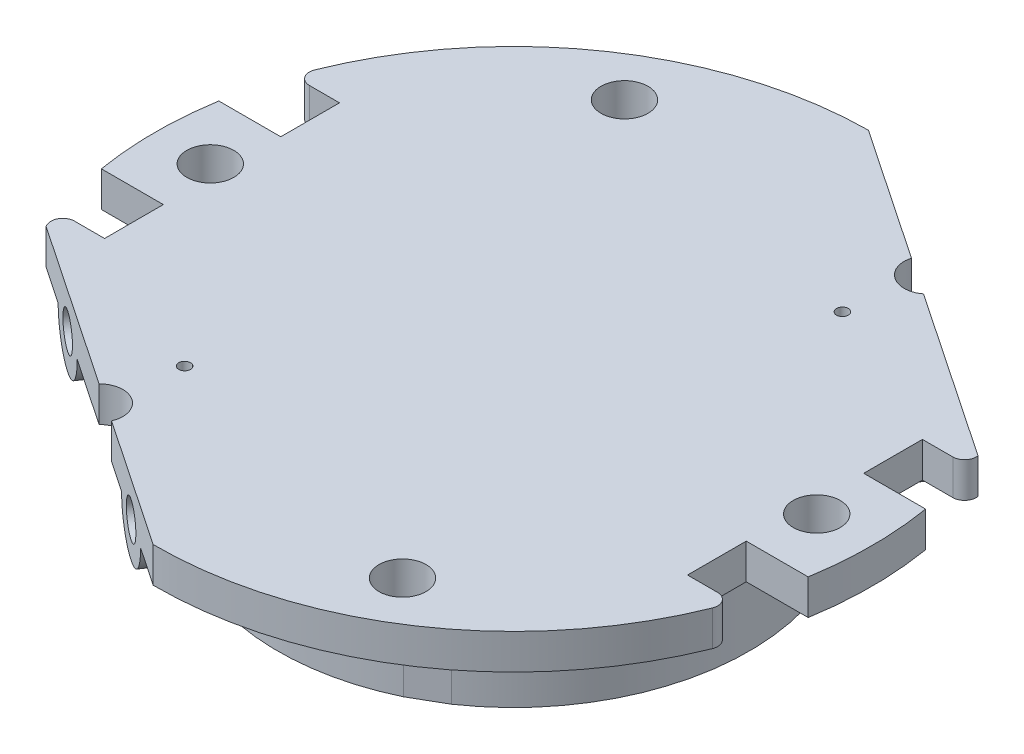
SolidWorks part; units mm, degrees
ref_plane "Alzado" through (0, 0, 0) normal (0, 0, 1) x (1, 0, 0)
ref_plane "Planta" through (0, 0, 0) normal (0, 1, 0) x (1, 0, 0)
ref_plane "Vista lateral" through (0, 0, 0) normal (1, 0, 0) x (0, 0, -1)
sketch "Croquis1" plane through (0, 0, 0) normal (0, 1, 0) x (1, 0, 0)
  circle A0 centre (0, 0) radius 30.5
extrude "Saliente-Extruir1" add sketch "Croquis1" along normal blind 3
sketch "Croquis5" plane through (0, 3, 0) normal (0, 1, 0) x (1, 0, 0)
  line L1 (28.8141, -5) -> (30.0874, -5)
  line L2 (28.8141, 5) -> (30.0874, 5)
  line L3 (-24.8141, 10) -> (-28.8141, 10)
  line L4 (24.8141, -5) -> (24.8141, -10)
  line L5 (-24.8141, -10) -> (-28.8141, -10)
  line L6 (24.8141, -5) -> (28.8141, -5)
  line L7 (24.8141, 5) -> (24.8141, 10)
  line L8 (-24.8141, 5) -> (-28.8141, 5)
  line L9 (-24.8141, 5) -> (-24.8141, 10)
  line L10 (-24.8141, -5) -> (-28.8141, -5)
  line L11 (-24.8141, -5) -> (-24.8141, -10)
  line L12 (24.8141, 5) -> (28.8141, 5)
  line L13 (24.8141, -10) -> (28.8141, -10)
  line L14 (24.8141, 10) -> (28.8141, 10)
  line L15 (-28.8141, 5) -> (-30.0874, 5)
  line L16 (-28.8141, -5) -> (-30.0874, -5)
  line L18 (-24.8141, 0) -> (-12.407, -21.4896)
  line L19 (-12.407, -21.4896) -> (12.407, -21.4896)
  line L20 (12.407, -21.4896) -> (24.8141, 0)
  line L21 (24.8141, 0) -> (12.407, 21.4896)
  line L22 (12.407, 21.4896) -> (-12.407, 21.4896)
  line L23 (-12.407, 21.4896) -> (-24.8141, 0)
  circle A0 centre (0, 0) radius 21.4896 construction
  circle A1 centre (0, 0) radius 30.5 construction
  arc A2 (-28.8141, 10) -> (-30.0874, 5) centre (0, 0) ccw
  arc A4 (-30.0874, -5) -> (-28.8141, -10) centre (0, 0) ccw
  arc A5 (30.0874, -5) -> (28.8141, -10) centre (0, 0) cw
  arc A6 (28.8141, 10) -> (30.0874, 5) centre (0, 0) cw
  circle M2 centre (0, 0) radius 30.5
extrude "Cortar-Extruir3" cut sketch "Croquis5" against normal blind 4 contours L10 L16 L5 L11 M2 | L15 L8 L9 L3 M2 | L14 L7 L12 L2 M2 | L4 L13 L1 L6 M2 region at (27.1844, 3, 7.3876) region at (-27.1844, 3, 7.3876) region at (27.1844, 3, -7.3876) region at (-27.1844, 3, -7.3876)
sketch "Croquis7" plane through (0, 3, 0) normal (0, 1, 0) x (1, 0, 0)
  line L2 (25.8141, 0) -> (12.907, 22.3556)
  line L3 (12.907, 22.3556) -> (-12.907, 22.3556)
  line L4 (-12.907, 22.3556) -> (-25.8141, 0)
  line L5 (-25.8141, 0) -> (-12.907, -22.3556)
  line L6 (-12.907, -22.3556) -> (12.907, -22.3556)
  line L7 (12.907, -22.3556) -> (25.8141, 0)
  circle A0 centre (25.8141, 0) radius 2
  circle A4 centre (-25.8141, 0) radius 2
  circle A5 centre (0, 0) radius 22.3556 construction
  circle A6 centre (12.907, 22.3556) radius 2
  circle A7 centre (-12.907, -22.3556) radius 2
  circle A8 centre (-12.907, 22.3556) radius 2
  circle A9 centre (12.907, -22.3556) radius 2
extrude "Cortar-Extruir4" cut sketch "Croquis7" against normal blind 10 contours A8 L4 L3 | A4 L4 L5 | A4 L5 L4 | A8 L3 L4 | L2 A6 L3 | L3 A6 L2 | L7 A0 L2 | L2 A0 L7 | A7 L5 L6 | A7 L6 L5 | L6 A9 L7 | L7 A9 L6 | A4 region at (24.7114, 3, 0) region at (26.3654, 3, 0) region at (12.3557, 3, -21.4007) region at (13.1827, 3, -22.8331) region at (13.1827, 3, 22.8331) region at (12.3557, 3, 21.4007) region at (-12.3557, 3, -21.4007) region at (-13.1827, 3, -22.8331) region at (-13.1827, 3, 22.8331) region at (-12.3557, 3, 21.4007) region at (-24.7114, 3, 0) region at (-26.3654, 3, 0)
sketch "Croquis8" plane through (0, 3, 0) normal (0, 1, 0) x (1, 0, 0)
  line L0 (0, 0) -> (12, 0)
  line L1 (12, 0) -> (12, 16)
  line L2 (0, 0) -> (-12, 0)
  line L3 (-12, 0) -> (-12, -16)
  circle A0 centre (12, 16) radius 0.5
  circle A1 centre (-12, -16) radius 0.5
extrude "Cortar-Extruir5" cut sketch "Croquis8" against normal blind 3 contours A1 | A0 region at (11.6564, 3, -16.3436) region at (-11.6564, 3, 15.6564)
sketch "Croquis9" plane through (0, 3, 0) normal (0, 1, 0) x (1, 0, 0)
  line L2 (-10, 17.3205) -> (-8.701, 18.0705)
  line L5 (25.6318, 16.5306) -> (27.1318, 13.9325)
  line L6 (-10, 17.3205) -> (-11.299, 16.5705)
  line L8 (10, -17.3205) -> (8.701, -18.0705)
  line L9 (10, -17.3205) -> (11.299, -16.5705)
  circle A0 centre (0, 0) radius 20.0562
  circle A1 centre (-12, -16) radius 3
  circle A2 centre (12, 16) radius 3
extrude "Saliente-Extruir2" add sketch "Croquis9" against normal blind 13 contours L2 L6 | L8 L9 region at (0, 3, 0)
sketch "Croquis11" plane through (14.0495, 0, -20.8293) normal (0.5592, 0, -0.829) x (-0.829, 0, -0.5592)
  line L1 (17.2916, 0) -> (-17.2916, 0)
  line L2 (17.2916, 0) -> (17.2916, 3)
  line L3 (17.2916, 3) -> (-17.2916, 3)
  line L4 (-17.2916, 0) -> (-17.2916, 3)
extrude "Saliente-Extruir3" add sketch "Croquis11" along normal blind 6
sketch "Croquis12" plane through (0, 3, 0) normal (0, 1, 0) x (1, 0, 0)
  circle A0 centre (12.907, 22.3556) radius 2
extrude "Cortar-Extruir7" cut sketch "Croquis12" against normal blind 3
sketch "Croquis13" plane through (17.4047, 0, -25.8035) normal (0.5592, 0, -0.829) x (-0.829, 0, -0.5592)
  line L0 (-17.2916, 0) -> (17.2916, 0)
  line L1 (17.2916, 3) -> (-17.2916, 3)
  line L2 (17.2916, 3) -> (-17.2916, 3) construction
  line L3 (17.2916, 0) -> (17.2916, 3) construction
  circle A1 centre (10, 0) radius 3
  circle A2 centre (-10, 0) radius 3
  circle A3 centre (10, 0) radius 1.5
  circle A5 centre (-10, 0) radius 1.5
  line M4 (-17.2916, 0) -> (17.2916, 0)
extrude "Saliente-Extruir4" add sketch "Croquis13" against normal blind 20 contours A3 L0 A1 | A3 L0 A1 | A5 L0 A2 | A5 L0 A2 | A5 M4 | A3 M4 region at (25.6951, 1.5671, -20.2116) region at (25.6951, -0.6366, -20.2116) region at (23.8297, -0.0671, -21.4698) region at (10.8337, 2.0739, -30.2358) region at (10.9797, -0.0671, -30.1373) region at (9.1143, -0.6366, -31.3955)
sketch "Croquis14" plane through (17.4047, 0, -25.8035) normal (0.5592, 0, -0.829) x (-0.829, 0, -0.5592)
  circle A0 centre (-10, 0) radius 1.5
  circle A1 centre (10, 0) radius 1.5
extrude "Cortar-Extruir8" cut sketch "Croquis14" against normal blind 6
sketch "Croquis15" plane through (0, 3, 0) normal (0, 1, 0) x (1, 0, 0)
  line L0 (28.3849, 11.16) -> (-0.2859, 30.4987)
  line L1 (28.3849, 11.16) -> (0.1409, -30.7136)
  line L2 (-0.2859, 30.4987) -> (-28.5299, -11.3749)
  line L3 (0.1409, -30.7136) -> (-28.5299, -11.3749)
  circle A0 centre (-0.2859, 0) radius 30.7165
  arc M12 (-28.8141, -10) -> (28.8141, -10) centre (0, 0) ccw
  circle M28 centre (-12.907, -22.3556) radius 2
extrude "Cortar-Extruir9" cut sketch "Croquis15" against normal blind 3 contours L3 M12 M28 region at (-15.494, 3, 22.7434)
sketch "Croquis16" plane through (-14.1945, 0, 21.0442) normal (-0.5592, 0, 0.829) x (0.829, 0, 0.5592)
  line L0 (-16.9088, 0) -> (-16.9088, 3)
  line L1 (-16.9088, 0) -> (16.78, 0)
  line L2 (-16.9088, 3) -> (16.78, 3)
  line L3 (16.78, 0) -> (16.78, 3)
extrude "Saliente-Extruir5" add sketch "Croquis16" along normal blind 6
sketch "Croquis17" plane through (0, 3, 0) normal (0, 1, 0) x (1, 0, 0)
  circle A0 centre (-12.907, -22.3556) radius 2
extrude "Cortar-Extruir10" cut sketch "Croquis17" against normal blind 3
sketch "Croquis18" plane through (-17.5497, 0, 26.0185) normal (-0.5592, 0, 0.829) x (0.829, 0, 0.5592)
  line L2 (-16.9088, 0) -> (16.78, 0) construction
  circle A0 centre (9.9356, 0) radius 3
  circle A1 centre (-10.0644, 0) radius 3
extrude "Saliente-Extruir6" add sketch "Croquis18" against normal blind 25
sketch "Croquis19" plane through (-17.5497, 0, 26.0185) normal (-0.5592, 0, 0.829) x (0.829, 0, 0.5592)
  circle A0 centre (-10.0644, 0) radius 1.5
  circle A1 centre (9.9356, 0) radius 1.5
extrude "Cortar-Extruir11" cut sketch "Croquis19" against normal blind 5
sketch "Croquis20" plane through (17.4047, 0, -25.8035) normal (0.5592, 0, -0.829) x (-0.829, 0, -0.5592)
  line L0 (17.2916, 3) -> (17.2916, 0)
  line L1 (17.2916, 0) -> (13, 0)
  line L2 (-7, 0) -> (7, 0) construction
  line L3 (7, 0) -> (-7, 0)
  line L4 (-13, 0) -> (-17.2916, 0)
  line L5 (-17.2916, 0) -> (-17.2916, 3)
  line L6 (-17.2916, 3) -> (17.2916, 3)
  arc A0 (13, 0) -> (7, 0) centre (10, 0) cw
  arc A1 (7, 0) -> (13, 0) centre (10, 0) ccw construction
  arc A2 (-7, 0) -> (-13, 0) centre (-10, 0) cw
extrude "Cortar-Extruir12" cut sketch "Croquis20" against normal blind 6
sketch "Croquis21" plane through (-17.5497, 0, 26.0185) normal (-0.5592, 0, 0.829) x (0.829, 0, 0.5592)
  line L0 (-13.0644, 0) -> (-16.9088, 0)
  line L1 (-16.9088, 0) -> (-16.9088, 3)
  line L2 (-16.9088, 3) -> (16.78, 3)
  line L3 (16.78, 3) -> (16.78, 0)
  line L4 (16.78, 0) -> (12.9356, 0)
  line L5 (6.9356, 0) -> (-7.0644, 0)
  arc A0 (-13.0644, 0) -> (-7.0644, 0) centre (-10.0644, 0) ccw
  arc A1 (6.9356, 0) -> (12.9356, 0) centre (9.9356, 0) ccw
extrude "Cortar-Extruir13" cut sketch "Croquis21" against normal blind 6
sketch "Croquis22" plane through (-14.1945, 0, 21.0442) normal (-0.5592, 0, 0.829) x (0.829, 0, 0.5592)
  circle A0 centre (-10.0644, 0) radius 1.5
  circle A1 centre (9.9356, 0) radius 1.5
extrude "Cortar-Extruir14" cut sketch "Croquis22" against normal blind 6
sketch "Croquis23" plane through (14.0495, 0, -20.8293) normal (0.5592, 0, -0.829) x (-0.829, 0, -0.5592)
  circle A0 centre (-10, 0) radius 1.5
  circle A1 centre (10, 0) radius 1.5
extrude "Cortar-Extruir15" cut sketch "Croquis23" against normal blind 6
fillet "Redondeo1" radius 1 4 edges at (-28.8141, 1.5, -10) (-28.8141, 1.5, 10) (28.8141, 1.5, 10) (28.8141, 1.5, -10)
sketch "Croquis24" plane through (0, 3, 0) normal (0, 1, 0) x (1, 0, 0)
  circle A0 centre (0, 0) radius 37.5
  circle A1 centre (0, 0) radius 34.5
  circle A2 centre (-12.907, -22.3556) radius 2
  circle A3 centre (12.907, 22.3556) radius 2
